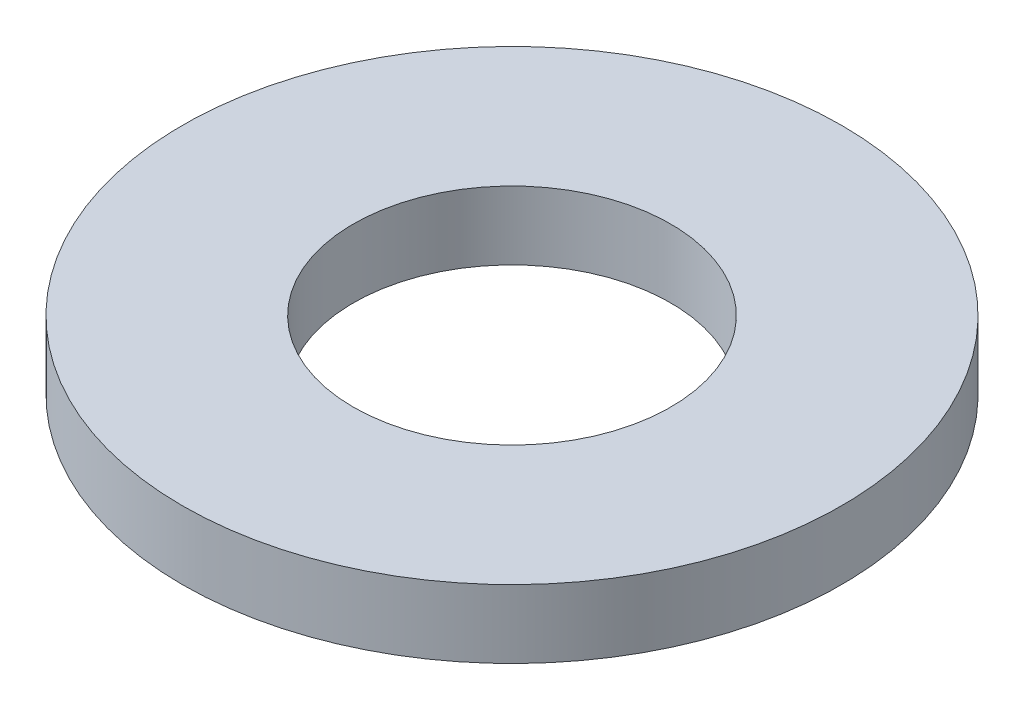
SolidWorks part; units mm, degrees
ref_plane "Front Plane" through (0, 0, 0) normal (0, 0, 1) x (1, 0, 0)
ref_plane "Top Plane" through (0, 0, 0) normal (0, 1, 0) x (1, 0, 0)
ref_plane "Right Plane" through (0, 0, 0) normal (1, 0, 0) x (0, 0, -1)
sketch "Sketch1" plane through (0, 0, 0) normal (0, 1, 0) x (1, 0, 0)
  circle A0 centre (0, 0) radius 67.5
  dimension "FLANGE_OD" = 135
extrude "Boss-Extrude1" add sketch "Sketch1" along normal blind 14
sketch "Sketch2" plane through (0, 0, 0) normal (0, 1, 0) x (1, 0, 0)
  circle A0 centre (0, 0) radius 32.5
  dimension "BORE_D" = 65
extrude "Cut-Extrude1" cut sketch "Sketch2" along normal through all
sketch "Sketch3" plane through (0, 14, 0) normal (0, 1, 0) x (1, 0, 0)
  circle A0 centre (0, 0) radius 27.1472 construction
  circle A1 centre (-27.1472, 0) radius 4.8055
  dimension "BOLT_D" = 9.6109
  dimension "BOLT_PCD" = 54.2943
extrude "Cut-Extrude2" cut sketch "Sketch3" against normal blind 13.5733 rebuild error yes
pattern_circular "CirPattern1" count 4 over 360 rebuild error yes
